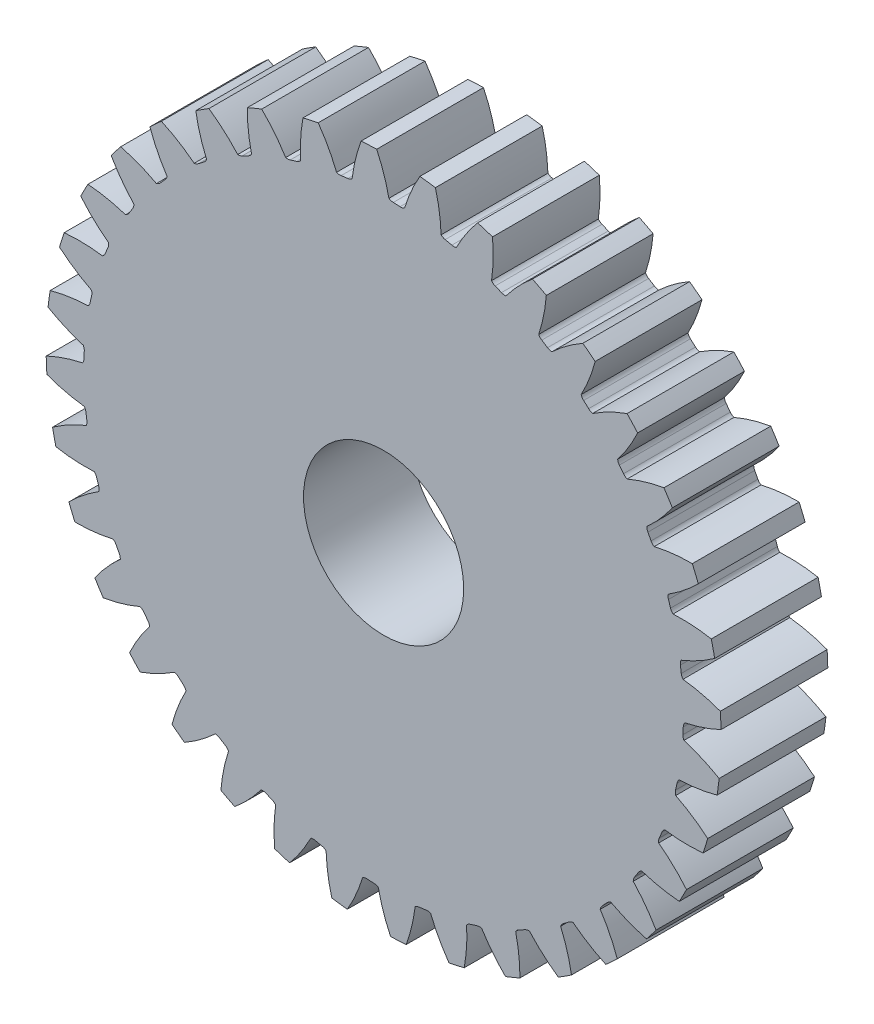
SolidWorks part; units mm, degrees
ref_plane "Front" through (0, 0, 0) normal (0, 0, 1) x (1, 0, 0)
ref_plane "Top" through (0, 0, 0) normal (0, 1, 0) x (1, 0, 0)
ref_plane "Right" through (0, 0, 0) normal (1, 0, 0) x (0, 0, -1)
sketch "Sketch1" plane through (0, 0, 0) normal (0, 0, 1) x (1, 0, 0)
  line L0 (-457.2, 0) -> (457.2, 0) construction
  circle A0 centre (0, 0) radius 10.033
  circle A1 centre (0, 0) radius 9.525 construction
  circle A3 centre (0, 0) radius 8.9128 construction
  dimension "D1" = 0.6122
  dimension "D2" = 1.1202
  dimension "D3" = 0.508
extrude "Boss-Extrude1" add sketch "Sketch1" against normal blind 3.175
sketch "Sketch2" plane through (0, 0, 0) normal (1, 0, 0) x (0, 0, -1)
  line L0 (3.175, 0) -> (9.525, 0)
  line L1 (3.175, 0) -> (3.175, 6.35)
  line L2 (3.175, 6.35) -> (9.525, 6.35)
  line L3 (9.525, 6.35) -> (9.525, 0)
  point P5 (9.525, -6.35)
  point P6 (0, -10.033)
  point P7 (3.175, -10.033)
  point P9 (0, 10.033)
revolve "Revolve1" [suppressed] add sketch "Sketch2" angle 360 mid plane about L0
fillet "Fillet2" [suppressed] radius 0.2007
sketch "Sketch3" plane through (0, 0, 0) normal (0, 0, 1) x (1, 0, 0)
  line L0 (0, 0) -> (0, 10.033) construction
  line L1 (-3.0613, 8.4108) -> (0, 9.525)
  line L2 (-9.5921, 9.525) -> (9.5921, 9.525) construction
  line L3 (-9.0136, 6.2443) -> (9.0136, 12.8057) construction
  line L4 (-3.0613, 8.4108) -> (0, 0) construction
  line L5 (-7.4633, 4.9409) -> (0, 0) construction
  line L6 (-7.4633, 4.9409) -> (-2.5179, 12.411) construction
  line L7 (-2.1265, 8.6943) -> (0, 0) construction
  line L8 (-2.1265, 8.6943) -> (0.0886, 9.2361) construction
  arc A0 (-3.0613, 8.4108) -> (-7.4633, 4.9409) centre (0, 0) ccw
  circle A1 centre (0, 0) radius 9.525 construction
  circle A2 centre (0, 0) radius 8.9506 construction
  arc A3 (-3.0613, 8.4108) -> (-2.1265, 8.6943) centre (0, 0) cw
  circle A4 centre (0, 0) radius 10.033 construction
  point P6 (0, 9.525)
  dimension "D1" = 3.2577
  dimension "D3" = 8.9588
  dimension "D5" = 2.2804
  dimension "D2" = 5.701
  dimension "D4" = 0.9773
sketch "Sketch4" plane through (0, 0, 0) normal (0, 0, 1) x (1, 0, 0)
  line L0 (0, 0) -> (0.4151, 9.5069) construction
  line L1 (0.1581, 8.9492) -> (0.1581, 8.9114)
  line L2 (0, 9.525) -> (0.8302, 9.4888) construction
  line L3 (0.6225, 8.9289) -> (0.6192, 8.8912)
  line L4 (0.1581, 8.9114) -> (0, 0) construction
  line L5 (0, 0) -> (0, 10.033) construction
  line L6 (-7.4633, 4.9409) -> (-2.5179, 12.411) construction
  line L7 (-7.4633, 4.9409) -> (-2.5179, 12.411) construction
  arc A0 (0.6192, 8.8912) -> (0.1581, 8.9114) centre (0, 0) ccw
  arc A1 (0, 9.525) -> (0.8302, 9.4888) centre (0, 0) cw construction
  circle A2 centre (0, 0) radius 9.525 construction
  circle A3 centre (0, 0) radius 8.9506 construction
  circle A4 centre (0, 0) radius 8.9128 construction
  arc A5 (3.59, 12.1443) -> (-2.5179, 12.411) centre (0, 0) ccw
  spline S0 degree 2 poles (-2.5179, 12.411) (-0.3011, 11.1182) (0.1581, 8.9492) knots 0 0 0 1 1 1
  spline S1 degree 2 poles (3.59, 12.1443) (1.269, 11.0497) (0.6225, 8.9289) knots 0 0 0 1 1 1
  dimension "D1" = 0.8312
extrude "Cut-Extrude1" cut sketch "Sketch4" against normal through all
fillet "Fillet1" radius 0.2494 2 edges at (0.6192, 8.8912, -1.5875) (0.1581, 8.9114, -1.5875)
pattern_circular "CirPattern1" count 36 over 360 about axis through (0, 0, -3.175) along (0, 0, 1) of "Cut-Extrude1", "Fillet1"
sketch "Sketch5" plane through (0, 0, 0) normal (0, 0, 1) x (1, 0, 0)
  circle A0 centre (0, 0) radius 2.3813
  circle A1 centre (0, 0) radius 2.3813 construction
  dimension "Bore Min" = 4.7625
  dimension "Bore Max" = 4.7625
extrude "Cut-Extrude2" cut sketch "Sketch5" against normal through all
chamfer "Chamfer1" [suppressed] distance 0.3175 angle 45
sketch "Pitch Dia" plane through (0, 0, 0) normal (0, 0, 1) x (1, 0, 0)
  circle A0 centre (0, 0) radius 9.525 construction
  circle A1 centre (0, 0) radius 9.525 construction
equation "\"D1@Boss-Extrude1\" = \"Face Wd@Sketch2\""
equation "\"D2@Sketch3\" = \"D1@Sketch3\"*1.75"
equation "\"D3@Sketch3\" = \"D1@Sketch3\"+\"D2@Sketch3\""
equation "\"D4@Sketch3\" = \"D1@Sketch3\"*.3"
equation "\"D5@Sketch3\" = \"D1@Sketch3\"-\"D4@Sketch3\""
equation "\"D1@Sketch4\" = 1.5708/(\"Number of Teeth@Sketch1\"/\"Ptich Dia@Sketch1\")"
equation "\"D1@Chamfer1\" = \"B Hub Dia@Sketch2\"*.025"
equation "\"D1@CirPattern1\" = \"Number of Teeth@Sketch1\""
equation "\"D1@Fillet1\" = \"D1@Sketch4\"*.3"
equation "\"D1@Fillet2\" = \"OD@Sketch1\"*.01"
equation "\"D1@Sketch1\" = 1.157/(\"Number of Teeth@Sketch1\"/\"Ptich Dia@Sketch1\")"
